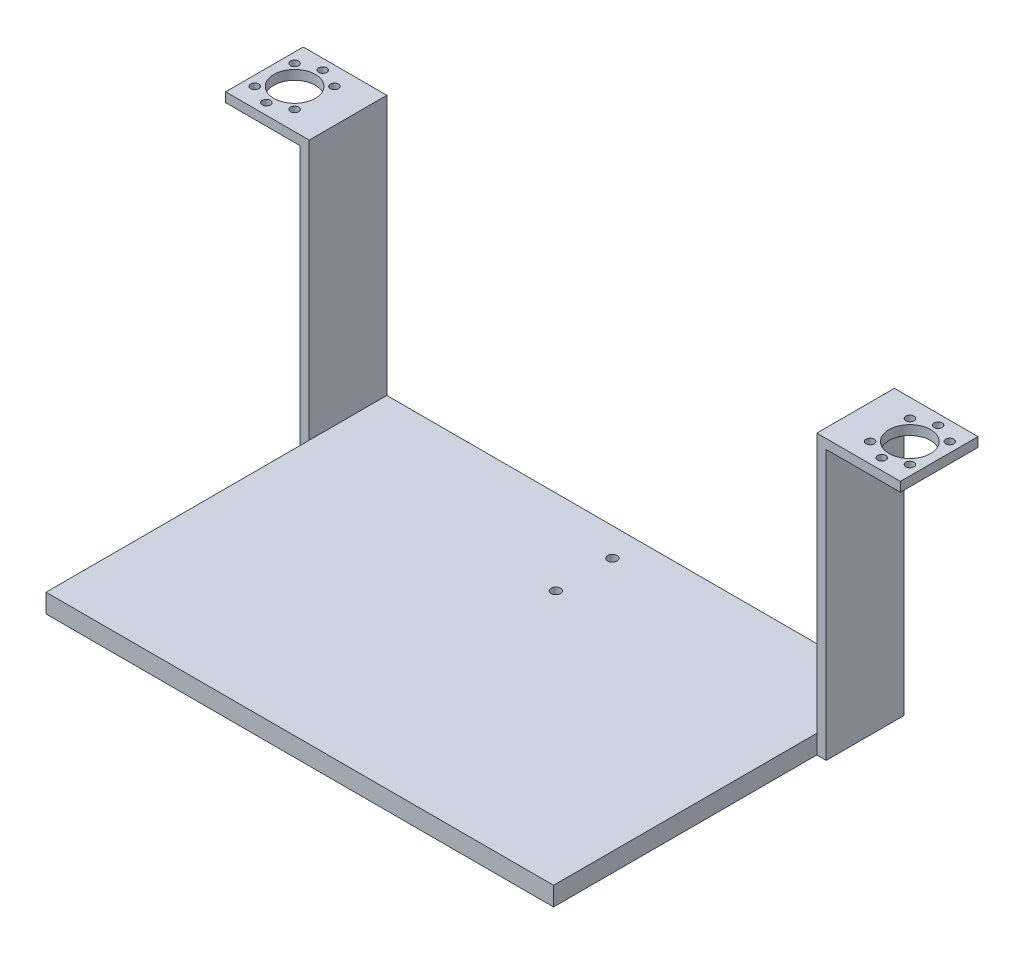
SolidWorks part; units mm, degrees
material "PE High Density"
ref_plane "Front Plane" through (0, 0, 0) normal (0, 0, 1) x (1, 0, 0)
ref_plane "Top Plane" through (0, 0, 0) normal (0, 1, 0) x (1, 0, 0)
ref_plane "Right Plane" through (0, 0, 0) normal (1, 0, 0) x (0, 0, -1)
sketch "Sketch1" plane through (0, 0, 0) normal (0, 1, 0) x (1, 0, 0)
  line L1 (0, 0) -> (454.914, 0)
  line L2 (0, 0) -> (0, 381)
  line L3 (0, 381) -> (454.914, 381)
  line L4 (454.914, 0) -> (454.914, 381)
  dimension "D1" = 454.914
  dimension "D2" = 381
extrude "Boss-Extrude1" add sketch "Sketch1" along normal blind 187.96
sketch "Sketch3" plane through (0, 187.96, 0) normal (0, 1, 0) x (1, 0, 0)
  line L1 (454.914, 0) -> (404.9014, 0)
  line L2 (454.914, 0) -> (454.914, 202.0062)
  line L3 (454.914, 202.0062) -> (404.9014, 202.0062)
  line L4 (404.9014, 0) -> (404.9014, 202.0062)
  line L5 (0, 0) -> (50.0126, 0)
  line L6 (0, 0) -> (0, 202.0062)
  line L7 (0, 202.0062) -> (50.0126, 202.0062)
  line L8 (50.0126, 0) -> (50.0126, 202.0062)
  dimension "D1" = 202.0062
  dimension "D2" = 50.0126
  dimension "D3" = 202.0062
  dimension "D4" = 50.0126
extrude "Cut-Extrude1" cut sketch "Sketch3" against normal through all
sketch "Sketch4" plane through (0, 187.96, 0) normal (0, 1, 0) x (1, 0, 0)
  line L0 (454.914, 381) -> (0, 381) construction
  line L1 (0, 381) -> (0, 202.0062) construction
  line L2 (454.914, 202.0062) -> (454.914, 381) construction
  circle A0 centre (20.066, 355.092) radius 14
  circle A1 centre (434.848, 355.092) radius 14
  dimension "D1" = 28
  dimension "D4" = 28
  dimension "D5" = 20.066
  dimension "D6" = 25.908
  dimension "D2" = 25.908
  dimension "D3" = 20.066
extrude "Cut-Extrude2" cut sketch "Sketch4" against normal through all
sketch "Sketch5" plane through (0, 187.96, 0) normal (0, 1, 0) x (1, 0, 0)
  line L0 (454.914, 381) -> (0, 381) construction
  line L1 (56.3626, 381) -> (398.5514, 381)
  line L2 (56.3626, 381) -> (56.3626, 0)
  line L3 (56.3626, 0) -> (398.5514, 0)
  line L4 (398.5514, 381) -> (398.5514, 0)
  line L5 (50.0126, 0) -> (404.9014, 0) construction
  line L6 (50.0126, 0) -> (50.0126, 202.0062) construction
  line L7 (404.9014, 202.0062) -> (404.9014, 0) construction
  dimension "D1" = 6.35
  dimension "D2" = 6.35
extrude "Cut-Extrude3" cut sketch "Sketch5" against normal blind 175.26
sketch "Sketch6" plane through (454.914, 0, 0) normal (1, 0, 0) x (0, 0, -1)
  line L0 (381, 187.96) -> (381, 0) construction
  line L1 (202.0062, 0) -> (381, 0)
  line L2 (202.0062, 0) -> (202.0062, 181.5974)
  line L3 (202.0062, 181.5974) -> (381, 181.5974)
  line L4 (381, 0) -> (381, 181.5974)
  dimension "D1" = 181.5974
extrude "Cut-Extrude4" cut sketch "Sketch6" against normal blind 50.0126
sketch "Sketch7" plane through (0, 0, 0) normal (-1, 0, 0) x (0, 0, 1)
  line L0 (-202.0062, 0) -> (-202.0062, 187.96) construction
  line L1 (-381, 0) -> (-202.0062, 0)
  line L2 (-381, 0) -> (-381, 181.5974)
  line L3 (-381, 181.5974) -> (-202.0062, 181.5974)
  line L4 (-202.0062, 0) -> (-202.0062, 181.5974)
  dimension "D1" = 181.5974
extrude "Cut-Extrude5" cut sketch "Sketch7" against normal blind 50.0126
sketch "Sketch10" plane through (404.9014, 0, 0) normal (1, 0, 0) x (0, 0, -1)
  line L0 (0, 0) -> (202.0062, 0)
  line L1 (202.0062, 187.96) -> (0, 187.96) construction
  line L3 (202.0062, 187.96) -> (202.0062, 0)
  line L5 (381, 0) -> (0, 0) construction
  line L8 (202.0062, 187.96) -> (0, 187.96)
  line L9 (0, 187.96) -> (0, 0)
  line L10 (202.0062, 181.5974) -> (202.0062, 187.96) construction
extrude "Cut-Extrude6" cut sketch "Sketch10" against normal through all
sketch "Sketch11" plane through (0, 187.96, 0) normal (0, 1, 0) x (1, 0, 0)
  line L0 (434.848, 385.1807) -> (434.848, 325.1677) construction
  line L1 (457.9437, 355.092) -> (408.0384, 355.092) construction
  line L2 (434.848, 355.1742) -> (453.5332, 373.8594) construction
  line L3 (434.848, 355.1742) -> (419.9379, 370.0843) construction
  line L4 (434.848, 355.1742) -> (452.7645, 337.2577) construction
  line L5 (434.848, 355.1742) -> (417.2384, 337.5646) construction
  circle A1 centre (434.848, 374.1742) radius 2.75
  circle A2 centre (448.283, 368.6092) radius 2.75
  circle A3 centre (421.413, 368.6092) radius 2.75
  circle A4 centre (448.283, 341.7392) radius 2.75
  circle A5 centre (434.848, 336.1742) radius 2.75
  circle A6 centre (421.413, 341.7392) radius 2.75
  dimension "D2" = 45
  dimension "D5" = 5.5
  dimension "D6" = 5.5
  dimension "D7" = 5.5
  dimension "D8" = 5.5
  dimension "D9" = 5.5
  dimension "D10" = 5.5
  dimension "D3" = 45
  dimension "D4" = 45
extrude "Cut-Extrude7" cut sketch "Sketch11" against normal through all
sketch "Sketch12" plane through (0, 187.96, 0) normal (0, 1, 0) x (1, 0, 0)
  line L0 (20.066, 355.092) -> (20.066, 379.9549) construction
  line L1 (20.066, 355.092) -> (42.2706, 355.092) construction
  line L2 (20.066, 355.092) -> (20.066, 337.1345) construction
  line L3 (20.066, 355.092) -> (2.8652, 355.092) construction
  line L4 (20.066, 355.092) -> (38.3107, 373.3367) construction
  line L5 (20.066, 355.092) -> (33.6036, 341.5544) construction
  line L6 (20.066, 355.092) -> (5.5449, 369.6131) construction
  line L7 (20.066, 355.092) -> (7.0967, 342.1227) construction
  circle A1 centre (20.066, 374.092) radius 2.75
  circle A2 centre (6.631, 368.527) radius 2.75
  circle A3 centre (33.501, 368.527) radius 2.75
  circle A4 centre (33.501, 341.657) radius 2.75
  circle A5 centre (20.066, 336.092) radius 2.75
  circle A6 centre (6.631, 341.657) radius 2.75
  dimension "D5" = 5.5
  dimension "D6" = 5.5
  dimension "D7" = 5.5
  dimension "D8" = 5.5
  dimension "D9" = 5.5
  dimension "D10" = 5.5
  dimension "D1" = 45
  dimension "D2" = 45
  dimension "45" = 45
  dimension "D3" = 45
extrude "Cut-Extrude8" cut sketch "Sketch12" against normal through all
sketch "Sketch13" plane through (398.5514, 0, 0) normal (1, 0, 0) x (0, 0, -1)
  line L0 (202.0062, 0) -> (151.2062, 0)
  line L2 (202.0062, 0) -> (202.0062, 181.5974) construction
  line L3 (202.0062, 12.7) -> (202.0062, 0)
  line L4 (151.2062, 0) -> (151.2062, 12.7)
  line L5 (151.2062, 12.7) -> (202.0062, 12.7)
  point P7 (0, 0)
  dimension "D1" = 50.8
  dimension "D2" = 12.7
extrude "Boss-Extrude2" add sketch "Sketch13" against normal up to surface (342.1888 mm away) up to face at (56.3626, 100.33, -291.5031)
sketch "Sketch15" plane through (0, 187.96, 0) normal (0, 1, 0) x (1, 0, 0)
  line L0 (398.5514, 328.676) -> (454.914, 328.676) construction
  line L1 (398.5514, 202.0062) -> (398.5514, 381) construction
  line L2 (454.914, 202.0062) -> (454.914, 381) construction
  line L3 (454.914, 381) -> (398.5514, 381) construction
  line L4 (0, 328.676) -> (56.3626, 328.676) construction
  line L5 (398.5514, 328.676) -> (454.914, 328.676)
  line L6 (398.5514, 328.676) -> (398.5514, 202.0062)
  line L7 (398.5514, 202.0062) -> (454.914, 202.0062)
  line L8 (454.914, 328.676) -> (454.914, 202.0062)
  line L9 (0, 381) -> (0, 202.0062) construction
  line L10 (56.3626, 381) -> (56.3626, 202.0062) construction
  line L11 (56.3626, 381) -> (0, 381) construction
  line L13 (56.3626, 202.0062) -> (0, 202.0062)
  line L14 (56.3626, 202.0062) -> (56.3626, 328.676)
  line L15 (56.3626, 328.676) -> (0, 328.676)
  line L16 (0, 202.0062) -> (0, 328.676)
  dimension "D1" = 52.324
  dimension "D2" = 52.324
extrude "Cut-Extrude9" cut sketch "Sketch15" against normal through all
sketch "Sketch16" plane through (0, 0, 0) normal (0, -1, 0) x (1, 0, 0)
  line L0 (227.457, -381) -> (227.457, -253.5221) construction
  line L1 (404.9014, -381) -> (50.0126, -381) construction
  circle A0 centre (227.457, -361.95) radius 3.175
  circle A1 centre (227.457, -323.85) radius 3.175
  dimension "D1" = 6.35
  dimension "D2" = 6.35
  dimension "D3" = 38.1
  dimension "D4" = 19.05
extrude "Cut-Extrude10" cut sketch "Sketch16" against normal through all
